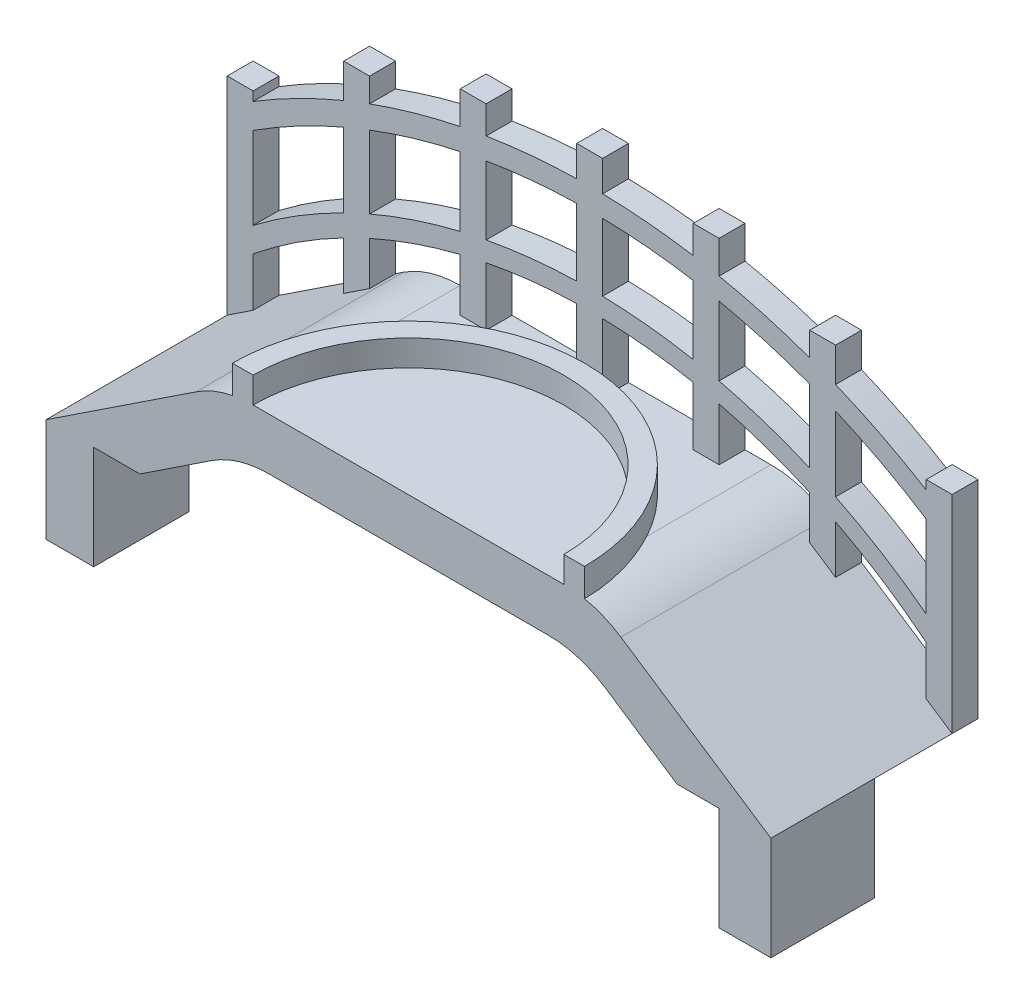
SolidWorks part; units mm, degrees
ref_plane "Front Plane" through (0, 0, 0) normal (0, 0, 1) x (1, 0, 0)
ref_plane "Top Plane" through (0, 0, 0) normal (0, 1, 0) x (1, 0, 0)
ref_plane "Right Plane" through (0, 0, 0) normal (1, 0, 0) x (0, 0, -1)
sketch "Sketch5" plane through (0, 0, 0) normal (0, 0, 1) x (1, 0, 0)
  line L0 (1.751, -2.6485) -> (10.1527, 2.906)
  line L1 (12.7, 7.134) -> (31.75, 7.134)
  line L2 (0, 0) -> (9.198, 6.081)
  line L3 (35.252, 6.081) -> (44.45, 0)
  line L4 (0, 0) -> (10.7907, 0) construction
  line L5 (44.45, 0) -> (33.6593, 0) construction
  line L6 (13.6546, 3.959) -> (30.7954, 3.959)
  line L7 (34.2973, 2.906) -> (42.699, -2.6485)
  line L8 (0, 0) -> (5.7571, 0)
  line L9 (44.45, 0) -> (38.6929, 0)
  line L10 (0, 0) -> (0, 9.525)
  line L11 (44.45, 0) -> (44.45, 9.525)
  line L12 (22.225, 7.134) -> (22.225, 16.659) construction
  line L13 (22.225, 7.134) -> (22.225, 3.959) construction
  line L14 (0, 0) -> (1.5875, 0)
  line L15 (0, 0) -> (0, 12.7)
  line L16 (0, 12.7) -> (1.5875, 12.7)
  line L17 (1.5875, 0) -> (1.5875, 12.7)
  line L18 (23.0187, 3.959) -> (21.4312, 3.959)
  line L19 (23.0187, 3.959) -> (23.0188, 19.834)
  line L20 (23.0188, 19.834) -> (21.4312, 19.834)
  line L21 (21.4312, 3.959) -> (21.4312, 19.834)
  line L22 (1.5875, 9.2118) -> (7.1438, 9.2118) construction
  line L23 (7.1437, 17.0604) -> (8.7312, 17.0604)
  line L24 (7.1437, 17.0604) -> (7.1438, 1.1854)
  line L25 (7.1438, 1.1854) -> (8.7313, 1.1854)
  line L26 (8.7312, 17.0604) -> (8.7313, 1.1854)
  line L27 (14.2875, 19.1598) -> (15.875, 19.1598)
  line L28 (14.2875, 19.1598) -> (14.2875, 3.2848)
  line L29 (14.2875, 3.2848) -> (15.875, 3.2848)
  line L30 (15.875, 19.1598) -> (15.875, 3.2848)
  line L31 (8.7313, 8.208) -> (14.2875, 8.208) construction
  line L32 (15.875, 13.1596) -> (21.4312, 13.1596) construction
  line L33 (7.9375, 17.0604) -> (7.9375, 13.8854) construction
  line L34 (15.0812, 19.1598) -> (15.0812, 15.9848) construction
  line L35 (44.45, 0) -> (38.6929, 0)
  line L36 (30.1625, 19.1598) -> (28.575, 19.1598)
  line L37 (30.1625, 19.1598) -> (30.1625, 3.2848)
  line L38 (28.575, 19.1598) -> (28.575, 3.2848)
  line L39 (30.1625, 3.2848) -> (28.575, 3.2848)
  line L40 (37.3062, 1.1854) -> (35.7187, 1.1854)
  line L41 (37.3062, 17.0604) -> (35.7187, 17.0604)
  line L42 (35.7187, 17.0604) -> (35.7187, 1.1854)
  line L43 (37.3062, 17.0604) -> (37.3062, 1.1854)
  line L44 (44.45, 12.7) -> (42.8625, 12.7)
  line L45 (44.45, 0) -> (44.45, 12.7)
  line L46 (44.45, 0) -> (44.45, 9.525)
  line L47 (42.8625, 0) -> (42.8625, 12.7)
  line L48 (11.7454, 3.959) -> (32.7046, 3.959) construction
  line L49 (32.7046, 3.959) -> (42.699, -2.6485) construction
  line L50 (10.7907, 7.134) -> (33.6593, 7.134) construction
  line L51 (33.6593, 7.134) -> (44.45, 0) construction
  line L52 (1.751, -2.6485) -> (11.7454, 3.959) construction
  line L53 (0, 0) -> (10.7907, 7.134) construction
  arc A0 (0, 9.525) -> (44.45, 9.525) centre (22.225, -21.5277) cw
  arc A1 (0, 11.1125) -> (44.45, 11.1125) centre (22.225, -21.5277) cw
  arc A2 (30.7954, 3.959) -> (34.2973, 2.906) centre (30.7954, -2.391) cw
  arc A3 (31.75, 7.134) -> (35.252, 6.081) centre (31.75, 0.784) cw
  arc A4 (10.1527, 2.906) -> (13.6546, 3.959) centre (13.6546, -2.391) cw
  arc A5 (12.7, 7.134) -> (9.198, 6.081) centre (12.7, 0.784) ccw
  point P65 (33.6593, 7.134)
  dimension "D12" = 6.35
  dimension "D2" = 19.05
  dimension "D1" = 44.45
  dimension "D3" = 3.175
  dimension "D4" = 9.525
  dimension "D5" = 1.5875
  dimension "D6" = 12.7
  dimension "D7" = 1.5875
  dimension "D8" = 15.875
  dimension "D9" = 12.7
  dimension "D10" = 3.175
  dimension "D11" = 1.5875
extrude "Boss-Extrude1" add sketch "Sketch5" along normal blind 12.7 contours L8 L17 L2 | L25 L24 L2 L17 L8 L0 | L26 L2 L24 L25 L0 | L1 A5 L2 L26 L0 A4 L6 L28 | L30 L1 L28 L6 | L1 L30 L6 L21 | L21 L6 L19 L1 | L38 L1 L19 L6 | L1 L38 L6 L37 | A3 L1 L37 L6 A2 L7 L42 L3 | L43 L3 L42 L7 L40 | L35 L47 L3 L43 L40 L7 | L47 L9 L3 region at (4.8921, 1.6908, 0) region at (7.9435, 3.3651, 0) region at (1.0583, 0.3498, 0) region at (11.4022, 5.0552, 0) region at (15.0812, 5.5465, 0) region at (18.6531, 5.5465, 0) region at (22.225, 5.5465, 0) region at (25.7969, 5.5465, 0) region at (29.3687, 5.5465, 0) region at (33.0478, 5.0552, 0) region at (36.5065, 3.3651, 0) region at (39.5579, 1.6908, 0) region at (43.3917, 0.3498, 0)
extrude "Boss-Extrude2" add sketch "Sketch5<4>" along normal blind 1.5875 separate body contours A1 L15 A0 L17 | A1 L17 A0 L24 | A1 L24 A0 L26 | A1 L26 A0 L28 | A1 L28 A0 L30 | A1 L30 A0 L21 | A1 L21 A0 L19 | A1 L19 A0 L38 | A1 L38 A0 L37 | A1 L37 A0 L42 | A1 L42 A0 L43 | A1 L43 A0 L47 | A1 L47 A0 L45 region at (0.7895, 10.851, 0) region at (4.3267, 12.8905, 0) region at (7.9352, 14.5811, 0) region at (11.4895, 15.7587, 0) region at (15.0802, 16.6439, 0) region at (18.647, 17.111, 0) region at (22.225, 17.3071, 0) region at (25.803, 17.111, 0) region at (29.3698, 16.6439, 0) region at (32.9605, 15.7587, 0) region at (36.5148, 14.5811, 0) region at (40.1233, 12.8905, 0) region at (43.6605, 10.851, 0)
sketch "Sketch5<4>" plane through (0, 0, 0) normal (0, 0, 1) x (1, 0, 0) same geometry as "Sketch5"
extrude "Boss-Extrude6" add sketch "Sketch5<7>" along normal blind 1.5875 contours L15 A1 L17 L16 | A0 L10 L2 L17 | A1 L15 A0 L17 | A0 L24 L2 L26 | L24 A1 L26 L23 | L26 L2 L24 L0 | L26 L0 L24 L25 | A1 L24 A0 L26 | L28 A1 L30 L27 | A1 L28 A0 L30 | A0 L28 L1 L30 | L30 L1 L28 L6 | L30 L6 L28 L29 | L21 L18 L19 L6 | L21 L6 L19 L1 | A0 L21 L1 L19 | L21 A1 L19 L20 | A1 L21 A0 L19 | L38 A1 L37 L36 | A0 L38 L1 L37 | L1 L38 L6 L37 | L39 L37 L6 L38 | L43 L7 L42 L40 | L43 L3 L42 L7 | A0 L42 L3 L43 | A1 L42 A0 L43 | L42 A1 L43 L41 | L47 A1 L45 L44 | A1 L47 A0 L45 | A0 L47 L3 L11 | L47 L9 L3 region at (7.9435, 3.3651, 0) region at (8.3375, 1.4457, 0) region at (0.7941, 5.2992, 0) region at (7.9312, 9.5615, 0) region at (0.7895, 10.851, 0) region at (7.9352, 14.5811, 0) region at (0.6663, 12.1261, 0) region at (15.0812, 5.5465, 0) region at (15.0812, 3.6219, 0) region at (7.8917, 16.1623, 0) region at (15.0858, 11.5584, 0) region at (15.0802, 16.6439, 0) region at (15.0604, 18.2312, 0) region at (22.225, 5.5465, 0) region at (22.225, 11.8951, 0) region at (22.225, 17.3071, 0) region at (22.225, 18.896, 0) region at (29.3687, 5.5465, 0) region at (29.3687, 3.6219, 0) region at (29.3642, 11.5584, 0) region at (29.3896, 18.2312, 0) region at (36.5188, 9.5615, 0) region at (36.5148, 14.5811, 0) region at (36.5583, 16.1623, 0) region at (36.5065, 3.3651, 0) region at (36.1125, 1.4457, 0) region at (43.6559, 5.2992, 0) region at (43.6605, 10.851, 0) region at (43.7837, 12.1261, 0) region at (43.3917, 0.3498, 0)
sketch "Sketch5<7>" plane through (0, 0, 0) normal (0, 0, 1) x (1, 0, 0) same geometry as "Sketch5"
sketch "Sketch6" plane through (0, 0, 0) normal (0, 0, -1) x (-1, 0, 0)
  line L0 (-44.45, 0) -> (-44.45, 12.7) construction
  line L1 (0, 0) -> (0, 12.7) construction
  line L2 (-44.45, 4.2704) -> (-44.45, 2.6829)
  line L3 (0, 2.6829) -> (0, 4.2704)
  arc A0 (-44.45, 4.2704) -> (0, 4.2704) centre (-22.225, -21.5277) cw
  arc A1 (-44.45, 2.6829) -> (0, 2.6829) centre (-22.225, -21.5277) cw
  arc A2 (-23.0187, 16.6507) -> (-28.575, 16.1273) centre (-22.225, -21.5277) ccw construction
  dimension "D1" = 1.5875
extrude "Boss-Extrude7" add sketch "Sketch6" against normal blind 1.5875
sketch "Sketch11" plane through (0, 7.134, 0) normal (0, 1, 0) x (1, 0, 0)
  line L1 (11.43, -12.7) -> (33.02, -12.7)
  circle A0 centre (22.225, -12.7) radius 9.525
  circle A1 centre (22.225, -12.7) radius 10.795
  point P2 (0, 0)
  line M9 (31.75, -12.7) -> (31.75, 0)
  line M19 (12.7, 0) -> (12.7, -12.7)
  dimension "D1" = 19.05
  dimension "D2" = 21.59
extrude "Boss-Extrude9" add sketch "Sketch11" along normal blind 1.5875 and the other way blind 0.254 contours A1 A0 M9 M19 | A1 L1 M19 | L1 A1 M9 region at (12.1893, 7.134, 10.7791) region at (12.919, 7.134, 10.16) region at (32.2607, 7.134, 10.7791)
sketch "Sketch12" plane through (0, 0, 0) normal (0, -1, 0) x (1, 0, 0)
  line L1 (0, 12.7) -> (2.921, 12.7)
  line L2 (0, 12.7) -> (0, 6.858)
  line L3 (0, 6.858) -> (2.921, 6.858)
  line L4 (2.921, 12.7) -> (2.921, 6.858)
  line L5 (44.45, 12.7) -> (41.275, 12.7)
  line L6 (44.45, 12.7) -> (44.45, 6.35)
  line L7 (44.45, 6.35) -> (41.275, 6.35)
  line L8 (41.275, 12.7) -> (41.275, 6.35)
  dimension "D1" = 2.921
  dimension "D2" = 5.842
  dimension "D3" = 6.35
  dimension "D4" = 3.175
extrude "Boss-Extrude10" add sketch "Sketch12" along normal blind 6.35
sketch "Sketch14" plane through (0, 0, 12.7) normal (0, 0, 1) x (1, 0, 0)
